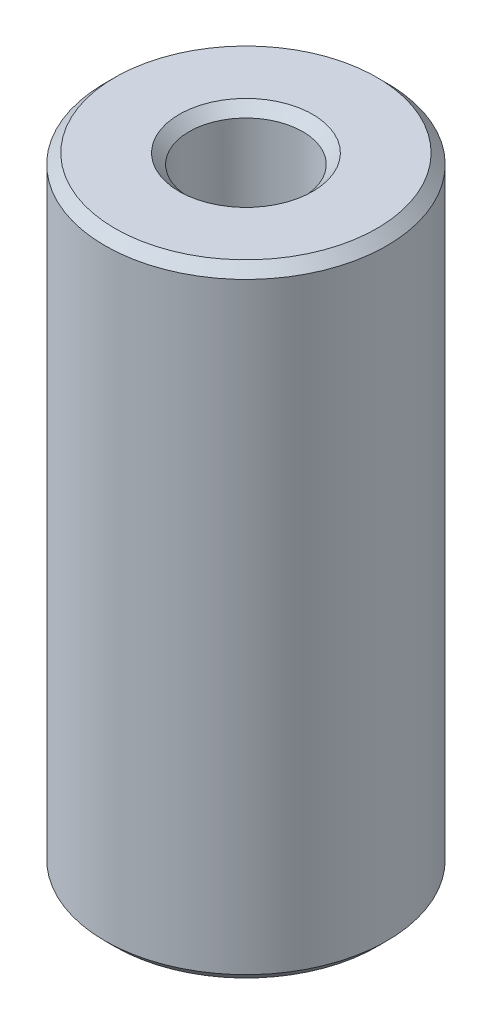
SolidWorks part; units mm, degrees
ref_plane "Front Plane" through (0, 0, 0) normal (0, 0, 1) x (1, 0, 0)
ref_plane "Top Plane" through (0, 0, 0) normal (0, 1, 0) x (1, 0, 0)
ref_plane "Right Plane" through (0, 0, 0) normal (1, 0, 0) x (0, 0, -1)
sketch "Sketch1" plane through (0, 0, 0) normal (0, 1, 0) x (1, 0, 0)
  circle A0 centre (0, 0) radius 22.5
  dimension "SLEEVE_OD" = 45
extrude "Boss-Extrude1" add sketch "Sketch1" along normal blind 99.3283
sketch "Sketch2" plane through (0, 0, 0) normal (0, 1, 0) x (1, 0, 0)
  circle A0 centre (0, 0) radius 9.0744
  dimension "BORE_D" = 18.1487
extrude "Cut-Extrude1" cut sketch "Sketch2" along normal through all
chamfer "Chamfer1" distance 1.5902 angle 45 4 edges at (0, 99.3283, 9.0744) (0, 0, 9.0744) (0, 0, 22.5) (0, 99.3283, 22.5)
